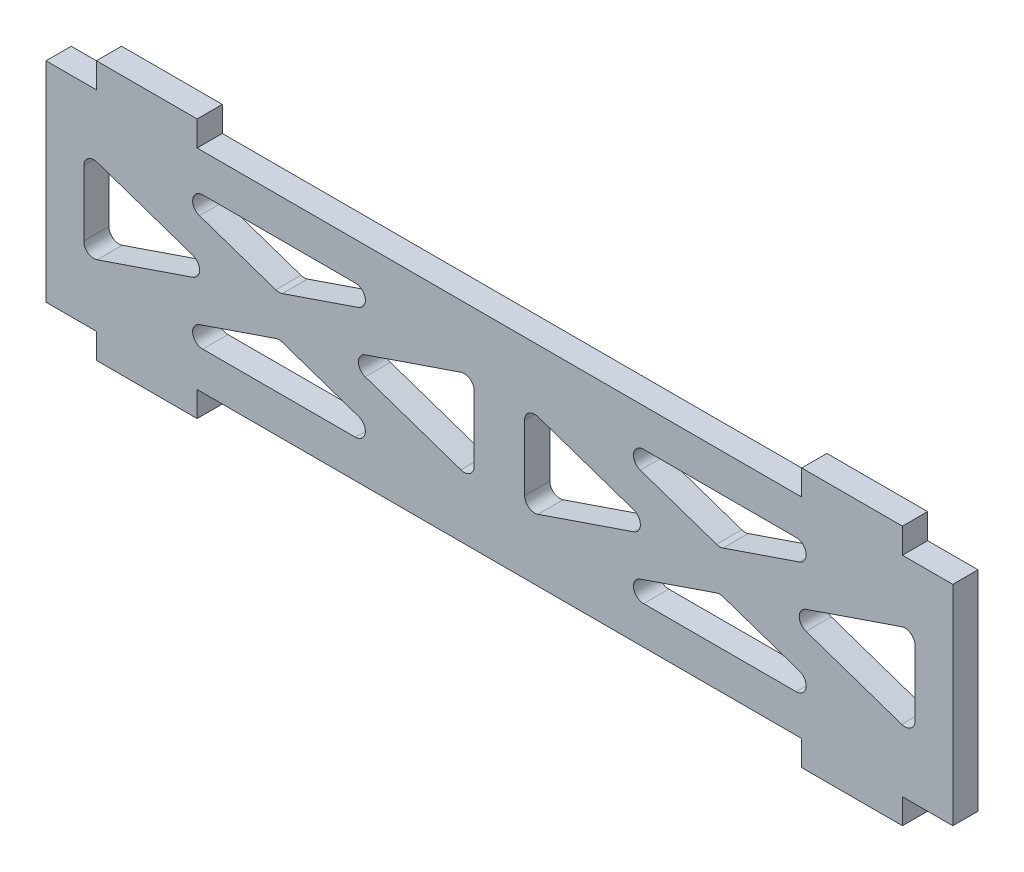
SolidWorks part; units mm, degrees
ref_plane "Front Plane" through (0, 0, 0) normal (0, 0, 1) x (1, 0, 0)
ref_plane "Top Plane" through (0, 0, 0) normal (0, 1, 0) x (1, 0, 0)
ref_plane "Right Plane" through (0, 0, 0) normal (1, 0, 0) x (0, 0, -1)
sketch "Sketch1" plane through (0, 0, 0) normal (0, 0, 1) x (1, 0, 0)
  line L0 (0, 0) -> (12.7, 0)
  line L1 (12.7, 0) -> (12.7, -6.35)
  line L2 (12.7, -6.35) -> (38.1, -6.35)
  line L3 (38.1, -6.35) -> (38.1, 0)
  line L4 (38.1, 0) -> (190.5, 0)
  line L5 (190.5, 0) -> (190.5, -6.35)
  line L6 (190.5, -6.35) -> (215.9, -6.35)
  line L7 (215.9, -6.35) -> (215.9, 0)
  line L8 (215.9, 0) -> (228.6, 0)
  line L9 (228.6, 0) -> (228.6, 52.72)
  line L10 (228.6, 26.36) -> (0, 26.36) construction
  line L11 (0, 52.72) -> (0, 0)
  line L12 (215.9, 52.72) -> (228.6, 52.72)
  line L13 (215.9, 59.07) -> (215.9, 52.72)
  line L14 (190.5, 59.07) -> (215.9, 59.07)
  line L15 (190.5, 52.72) -> (190.5, 59.07)
  line L16 (38.1, 52.72) -> (190.5, 52.72)
  line L17 (38.1, 59.07) -> (38.1, 52.72)
  line L18 (12.7, 59.07) -> (38.1, 59.07)
  line L19 (12.7, 52.72) -> (12.7, 59.07)
  line L20 (0, 52.72) -> (12.7, 52.72)
  line L21 (-38.1, 59.07) -> (349.25, 59.07) construction
  point P12 (228.6, 36.6944)
  point P14 (228.6, 32.9157)
  dimension "D1" = 12.7
  dimension "D2" = 6.35
  dimension "D3" = 25.4
  dimension "D4" = 152.4
  dimension "D5" = 12.7
extrude "Boss-Extrude1" add sketch "Sketch1" along normal blind 6.35
sketch "Sketch2" plane through (0, 0, 6.35) normal (0, 0, 1) x (1, 0, 0)
  line L0 (9.525, 43.195) -> (219.075, 43.195)
  line L1 (0, 52.72) -> (228.6, 52.72) construction
  line L2 (0, 52.72) -> (0, 0) construction
  line L3 (0, 0) -> (228.6, 0) construction
  line L4 (228.6, 52.72) -> (228.6, 0) construction
  line L5 (219.075, 43.195) -> (219.075, 9.525)
  line L6 (9.525, 9.525) -> (219.075, 9.525)
  line L7 (9.525, 43.195) -> (9.525, 9.525)
  line L8 (114.3, 52.72) -> (114.3, 0) construction
  line L9 (107.95, 52.72) -> (107.95, 0)
  line L10 (120.65, 52.72) -> (120.65, 0)
  line L11 (9.525, 43.195) -> (107.95, 9.525) construction
  line L12 (11.0665, 47.7011) -> (109.4915, 14.0311)
  line L13 (7.9835, 38.6889) -> (106.4085, 5.0189)
  line L14 (9.525, 9.525) -> (107.95, 43.195) construction
  line L15 (7.9835, 14.0311) -> (106.4085, 47.7011)
  line L16 (11.0665, 5.0189) -> (109.4915, 38.6889)
  line L17 (219.075, 43.195) -> (120.65, 9.525) construction
  line L18 (217.5335, 47.7011) -> (119.1085, 14.0311)
  line L19 (220.6165, 38.6889) -> (122.1915, 5.0189)
  line L20 (219.075, 9.525) -> (120.65, 43.195) construction
  line L21 (220.6165, 14.0311) -> (122.1915, 47.7011)
  line L22 (217.5335, 5.0189) -> (119.1085, 38.6889)
  arc A0 (11.0665, 47.7011) -> (7.9835, 38.6889) centre (9.525, 43.195) ccw
  arc A1 (106.4085, 5.0189) -> (109.4915, 14.0311) centre (107.95, 9.525) ccw
  arc A2 (7.9835, 14.0311) -> (11.0665, 5.0189) centre (9.525, 9.525) ccw
  arc A3 (109.4915, 38.6889) -> (106.4085, 47.7011) centre (107.95, 43.195) ccw
  arc A4 (217.5335, 47.7011) -> (220.6165, 38.6889) centre (219.075, 43.195) cw
  arc A5 (122.1915, 5.0189) -> (119.1085, 14.0311) centre (120.65, 9.525) cw
  arc A6 (220.6165, 14.0311) -> (217.5335, 5.0189) centre (219.075, 9.525) cw
  arc A7 (119.1085, 38.6889) -> (122.1915, 47.7011) centre (120.65, 43.195) cw
  point P16 (58.7375, 26.36)
  point P22 (58.7375, 26.36)
  point P28 (0, 0)
  point P30 (169.8625, 26.36)
  point P36 (169.8625, 26.36)
  dimension "D3" = 4.7625
  dimension "D2" = 12.7
  dimension "D1" = 9.525
extrude "Cut-Extrude1" cut sketch "Sketch2" against normal through all contours L7 L15 L13 | L12 L15 L0 | L16 L12 L9 | L16 L6 L13 | L18 L22 L10 | L21 L18 L0 | L21 L5 L19 | L6 L22 L19 region at (58.7375, 39.2612, 6.35) region at (21.0245, 26.36, 6.35) region at (96.4505, 26.36, 6.35) region at (58.7375, 13.4588, 6.35) region at (169.8625, 39.2612, 6.35) region at (132.1495, 26.36, 6.35) region at (207.5755, 26.36, 6.35) region at (169.8625, 13.4588, 6.35)
fillet "Fillet1" radius 2.54 24 edges at (120.65, 14.5585, 3.175) (120.65, 38.1615, 3.175) (155.1486, 26.36, 3.175) (107.95, 38.1615, 3.175) (107.95, 14.5585, 3.175) (73.4514, 26.36, 3.175) (169.8625, 21.3265, 3.175) (204.3611, 9.525, 3.175) (135.3639, 9.525, 3.175) (184.5764, 26.36, 3.175) (219.075, 38.1615, 3.175) (219.075, 14.5585, 3.175) (44.0236, 26.36, 3.175) (9.525, 14.5585, 3.175) (9.525, 38.1615, 3.175) (135.3639, 43.195, 3.175) (204.3611, 43.195, 3.175) (169.8625, 31.3935, 3.175) (93.2361, 43.195, 3.175) (24.2389, 43.195, 3.175) (58.7375, 21.3265, 3.175) (93.2361, 9.525, 3.175) (24.2389, 9.525, 3.175) (58.7375, 31.3935, 3.175)
